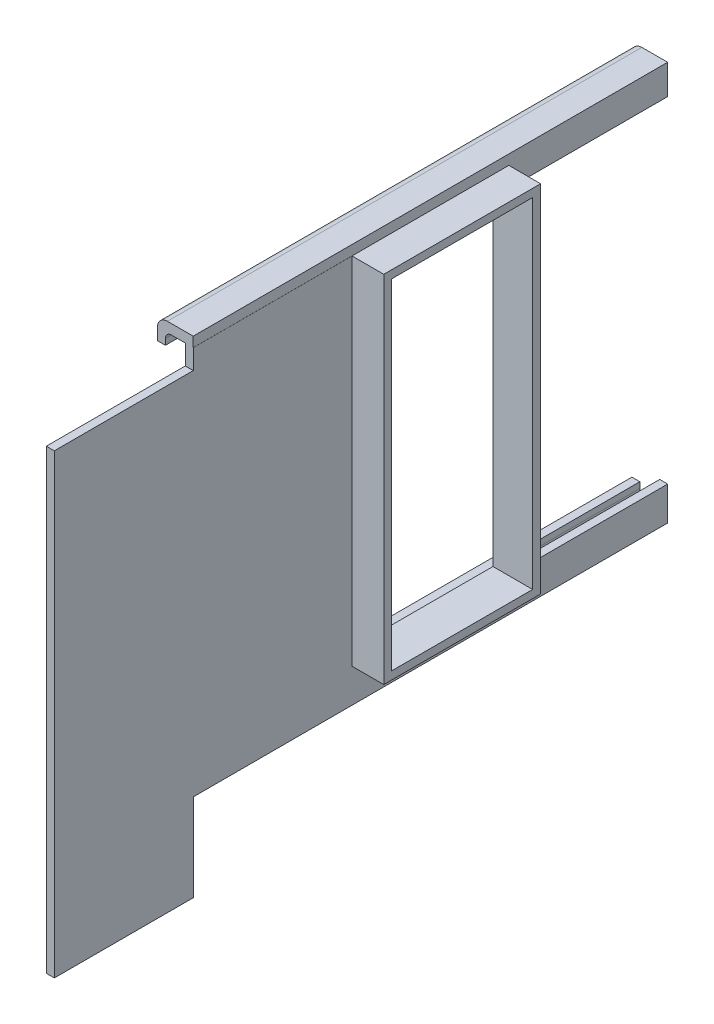
SolidWorks part; units mm, degrees
ref_plane "Front Plane" through (0, 0, 0) normal (0, 0, 1) x (1, 0, 0)
ref_plane "Top Plane" through (0, 0, 0) normal (0, 1, 0) x (1, 0, 0)
ref_plane "Right Plane" through (0, 0, 0) normal (1, 0, 0) x (0, 0, -1)
sketch "Sketch1" plane through (75.5364, 0, 0) normal (-1, 0, 0) x (0, 0, 1)
  line L4 (7.9, 43.5) -> (-7.9, 43.5)
  line L5 (-7.9, 43.5) -> (-7.9, 79.3)
  line L6 (-7.9, 79.3) -> (7.9, 79.3)
  line L7 (7.9, 79.3) -> (7.9, 43.5)
  line L8 (-8, 79.4) -> (8, 79.4) construction
  line L9 (8, 79.4) -> (8, 43.4) construction
  line L10 (-8, 43.4) -> (-8, 79.4) construction
  line L11 (8, 43.4) -> (-8, 43.4) construction
  dimension "D1" = 0.1
  dimension "D2" = 0.1
  dimension "D3" = 0.1
  dimension "D4" = 0.1
extrude "Extrude-Thin1" add sketch "Sketch1" against normal blind 3 and the other way blind 1 thin thin type one direction reverse wall 0.8
sketch "Sketch2" plane through (78.5364, 0, 0) normal (1, 0, 0) x (0, 0, -1)
  line L0 (7.9, 43.5) -> (-7.9, 43.5) construction
  line L1 (-7.9, 43.5) -> (-7.9, 79.3) construction
  line L2 (-7.9, 79.3) -> (7.9, 79.3) construction
  line L3 (7.9, 79.3) -> (7.9, 43.5) construction
  line L4 (7.9, 43.5) -> (-7.9, 43.5)
  line L5 (-7.9, 43.5) -> (-7.9, 79.3)
  line L6 (-7.9, 79.3) -> (7.9, 79.3)
  line L7 (7.9, 79.3) -> (7.9, 43.5)
sketch "Sketch3" plane through (74.5364, 0, 0) normal (-1, 0, 0) x (0, 0, 1)
  line L0 (7.9, 79.3) -> (23.9, 79.3)
  line L1 (23.9, 79.3) -> (23.9, 80.3)
  line L2 (23.9, 80.3) -> (-23.9, 80.3)
  line L3 (-23.9, 80.3) -> (-23.9, 79.3)
  line L5 (-23.9, 79.3) -> (-7.9, 79.3)
  line L6 (-7.9, 79.3) -> (7.9, 79.3)
  dimension "D1" = 16
  dimension "D2" = 16
  dimension "D3" = 1
extrude "Boss-Extrude1" add sketch "Sketch3" against normal blind 0.8
sketch "Sketch4" plane through (74.5364, 0, 0) normal (-1, 0, 0) x (0, 0, 1)
  line L1 (-23.9, 80.3) -> (23.9, 80.3)
  line L2 (-23.9, 80.3) -> (-23.9, 79.3)
  line L3 (-23.9, 79.3) -> (23.9, 79.3)
  line L4 (23.9, 80.3) -> (23.9, 79.3)
extrude "Boss-Extrude2" add sketch "Sketch4" along normal blind 2.8
sketch "Sketch5" plane through (0, 0, 7.9) normal (0, 0, 1) x (1, 0, 0)
  line L0 (75.3428, 0.2) -> (75.3428, 88.4) construction
  line L1 (74.5364, 79.3) -> (75.3428, 79.3)
  line L2 (74.5364, 79.3) -> (74.5364, 77.3)
  line L3 (74.5364, 77.3) -> (75.3428, 77.3)
  line L4 (75.3428, 79.3) -> (75.3428, 77.3)
  dimension "D1" = 2
extrude "Boss-Extrude3" add sketch "Sketch5" along normal blind 16
sketch "Sketch6" plane through (0, 0, -7.9) normal (0, 0, -1) x (-1, 0, 0)
  line L0 (-74.5364, 79.3) -> (-74.5364, 43.5) construction
  line L1 (-75.3364, 79.3) -> (-74.5364, 79.3)
  line L2 (-75.3364, 79.3) -> (-75.3364, 77.3)
  line L3 (-75.3364, 77.3) -> (-74.5364, 77.3)
  line L4 (-74.5364, 79.3) -> (-74.5364, 77.3)
  dimension "D1" = 2
extrude "Boss-Extrude4" add sketch "Sketch6" along normal blind 16
sketch "Sketch7" plane through (0, 79.3, 0) normal (0, -1, 0) x (1, 0, 0)
  line L1 (74.5364, -23.9) -> (71.7364, -23.9) construction
  line L2 (71.7364, -23.9) -> (71.7364, 23.9) construction
  line L3 (71.7364, -23.9) -> (72.5364, -23.9)
  line L4 (71.7364, -23.9) -> (71.7364, 23.9)
  line L5 (71.7364, 23.9) -> (72.5364, 23.9)
  line L6 (72.5364, -23.9) -> (72.5364, 23.9)
  dimension "D1" = 0.8
extrude "Boss-Extrude5" add sketch "Sketch7" along normal blind 1.2
sketch "Sketch8" plane through (0, 0, 7.9) normal (0, 0, 1) x (1, 0, 0)
  line L1 (75.3428, 77.3) -> (74.5364, 77.3)
  line L2 (75.3428, 77.3) -> (75.3428, 43.5)
  line L3 (75.3428, 43.5) -> (74.5364, 43.5)
  line L4 (74.5364, 77.3) -> (74.5364, 43.5)
extrude "Boss-Extrude6" add sketch "Sketch8" along normal blind 30
sketch "Sketch9" plane through (0, 0, 23.9) normal (0, 0, 1) x (1, 0, 0)
  line L0 (75.3428, 77.3) -> (75.3428, 79.3) construction
  line L1 (75.3428, 45.3) -> (74.5364, 45.3)
  line L2 (75.3428, 45.3) -> (75.3428, 57.3)
  line L3 (75.3428, 57.3) -> (74.5364, 57.3)
  line L4 (74.5364, 45.3) -> (74.5364, 57.3)
  line L5 (74.5364, 79.3) -> (74.5364, 77.3) construction
  line L6 (74.5364, 43.5) -> (75.3428, 43.5) construction
  dimension "D1" = 1.8
  dimension "D2" = 12
extrude "Boss-Extrude7" add sketch "Sketch9" along normal blind 10
sketch "Sketch12" plane through (74.5364, 0, 0) normal (-1, 0, 0) x (0, 0, 1)
  point P0 (31.6186, 52.4233)
fillet "Fillet1" radius 1 1 edges at (71.7364, 80.3, 0)
sketch "Sketch18" plane through (74.5364, 0, 0) normal (-1, 0, 0) x (0, 0, 1)
  line L3 (32.9, 45.3) -> (27.9, 45.3)
  line L4 (33.9, 54.3) -> (33.9, 46.3)
  line L5 (32.9, 55.3) -> (27.9, 55.3)
  line L6 (30.4, 55.3) -> (30.4, 45.3) construction
  line L7 (26.9, 54.3) -> (26.9, 46.3)
  line L8 (37.9, 77.3) -> (37.9, 43.5) construction
  line L9 (-7.9, 43.5) -> (37.9, 43.5) construction
  arc A2 (32.9, 45.3) -> (33.9, 46.3) centre (32.9, 46.3) ccw
  arc A3 (33.9, 54.3) -> (32.9, 55.3) centre (32.9, 54.3) ccw
  arc A4 (27.9, 45.3) -> (26.9, 46.3) centre (27.9, 46.3) cw
  arc A5 (26.9, 54.3) -> (27.9, 55.3) centre (27.9, 54.3) cw
  dimension "D5" = 1
  dimension "D6" = 1
  dimension "D7" = 8
  dimension "D1" = 7
  dimension "D2" = 10
  dimension "D3" = 4
  dimension "D4" = 1.8
  dimension "D8" = 5
  dimension "D9" = 1.4142
  dimension "D10" = 1.4142
extrude "Boss-Extrude8" add sketch "Sketch18" along normal blind 4
sketch "Sketch19" plane through (75.3428, 0, 0) normal (1, 0, 0) x (0, 0, -1)
  line L1 (-37.9, 31.3) -> (-23.9, 31.3)
  line L4 (-23.9, 77.3) -> (-23.9, 79.3) construction
  line L8 (-37.9, 31.3) -> (-37.9, 43.5)
  line L9 (-37.9, 43.5) -> (-23.9, 43.5)
  line L10 (-37.9, 43.5) -> (-7.9, 43.5) construction
  line L11 (-23.9, 43.5) -> (-23.9, 31.3)
  dimension "D1" = 12.2
extrude "Boss-Extrude9" add sketch "Sketch19" against normal up to surface (0.8064 mm away)
fillet "Fillet2" radius 0.6 1 edges at (72.5364, 79.3, 0)
sketch "Sketch21" plane through (74.5364, 0, 0) normal (-1, 0, 0) x (0, 0, 1)
  line L2 (26.9, 31.3) -> (26.9, 41.1)
  line L4 (-23.9, 79.3) -> (23.9, 79.3) construction
  line L5 (26.9, 41.1) -> (33.9, 41.1)
  line L7 (33.9, 41.1) -> (33.9, 31.3)
  line L8 (33.9, 46.3) -> (33.9, 54.3) construction
  line L9 (26.9, 54.3) -> (26.9, 46.3) construction
  line L10 (26.9, 31.3) -> (33.9, 31.3)
  dimension "D1" = 38.2
  dimension "D2" = 9.8
extrude "Boss-Extrude10" add sketch "Sketch21" along normal up to surface (4 mm away) up to face at (70.5364, 50.3, 30.4)
sketch "Sketch22" plane through (0, 0, -7.9) normal (0, 0, -1) x (-1, 0, 0)
  line L0 (-70.5364, 41.1) -> (-74.5364, 41.1) construction
  line L1 (-75.3428, 43.5) -> (-74.5364, 43.5)
  line L2 (-75.3428, 43.5) -> (-75.3428, 41.1)
  line L3 (-75.3428, 41.1) -> (-74.5364, 41.1)
  line L4 (-74.5364, 43.5) -> (-74.5364, 41.1)
  line L5 (-74.5364, 77.3) -> (-74.5364, 79.3) construction
  point P6 (0, 0)
extrude "Boss-Extrude11" add sketch "Sketch22" along normal up to surface (16 mm away) and the other way up to surface (31.8 mm away) up to face at (73.3833, 78.8331, -23.9) other way up to face at (73.7099, 78.9109, 23.9)
sketch "Sketch23" plane through (0, 0, 26.9) normal (0, 0, -1) x (-1, 0, 0)
  line L0 (-71.7364, 79.3) -> (-71.7364, 78.1) construction
  line L1 (-75.3428, 41.1) -> (-71.7364, 41.1)
  line L2 (-75.3428, 41.1) -> (-75.3428, 40.1)
  line L3 (-75.3428, 40.1) -> (-71.7364, 40.1)
  line L4 (-71.7364, 41.1) -> (-71.7364, 40.1)
  line L6 (-75.3428, 31.3) -> (-75.3428, 41.1) construction
  line L7 (-70.5364, 41.1) -> (-74.5364, 41.1) construction
  point P8 (0, 0)
  point P9 (0, 0)
  dimension "D1" = 1
extrude "Boss-Extrude12" add sketch "Sketch23" along normal up to surface (50.8 mm away) up to face at (74.9396, 42.3, -23.9)
sketch "Sketch24" plane through (0, 0, -23.9) normal (0, 0, -1) x (-1, 0, 0)
  line L1 (-71.7364, 41.1) -> (-72.5364, 41.1)
  line L2 (-71.7364, 41.1) -> (-71.7364, 42.3)
  line L3 (-71.7364, 42.3) -> (-72.5364, 42.3)
  line L4 (-72.5364, 41.1) -> (-72.5364, 42.3)
  line L6 (-71.7364, 41.1) -> (-74.5364, 41.1) construction
  line L7 (-71.7364, 79.3) -> (-71.7364, 78.1) construction
  point P7 (-71.9154, 41.4121)
  point P9 (0, 0)
  dimension "D1" = 1.2
extrude "Boss-Extrude13" add sketch "Sketch24" against normal up to surface (47.8 mm away) up to face at (73.7099, 78.9109, 23.9)
fillet "Fillet3" radius 0.6 1 edges at (72.5364, 41.1, 0)
sketch "Sketch25" plane through (71.7364, 0, 0) normal (-1, 0, 0) x (0, 0, 1)
  line L0 (26.9, 40.1) -> (18.6562, 40.1)
  line L1 (-23.9, 40.1) -> (26.9, 40.1) construction
  line L2 (18.6562, 40.1) -> (18.6562, 42.3)
  line L3 (23.9, 42.3) -> (-23.9, 42.3) construction
  line L4 (18.6562, 42.3) -> (23.9, 42.3)
  line L5 (23.9, 42.3) -> (23.9, 41.1)
  line L6 (23.9, 41.1) -> (26.9, 41.1)
  line L7 (26.9, 41.1) -> (26.9, 40.1)
extrude "Boss-Extrude14" add sketch "Sketch25" along normal up to surface (1.2 mm away) up to face at (70.5364, 36.2, 30.4)
fillet "Fillet4" radius 0.6 2 edges at (71.8364, 41.1, 23.9) (71.7364, 41.2, 18.6562)
